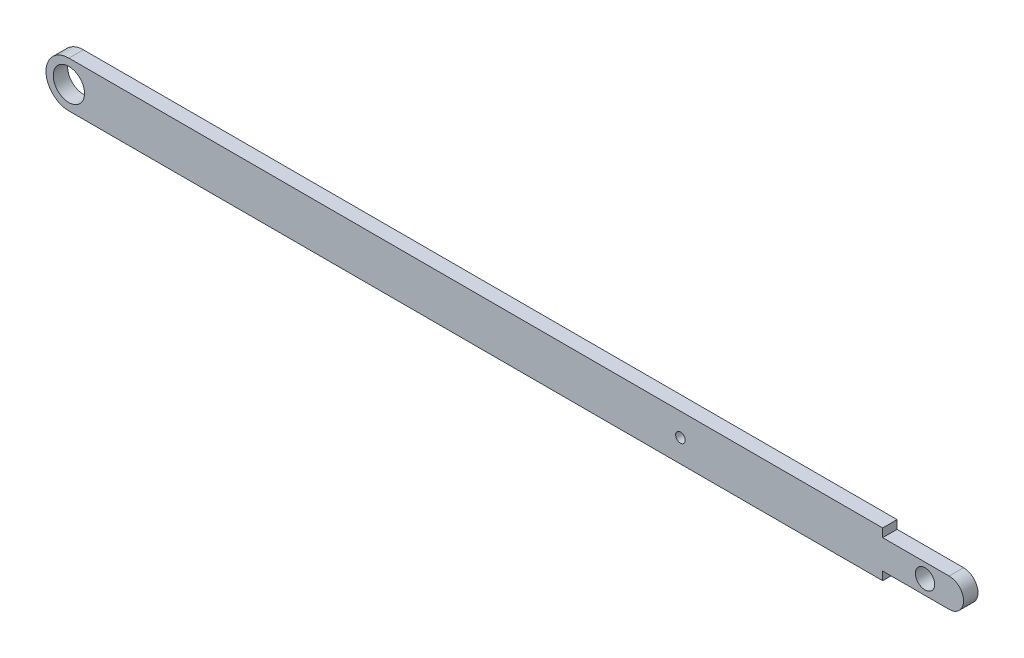
SolidWorks part; units mm, degrees
material "Gray Cast Iron"
ref_plane "Front Plane" through (0, 0, 0) normal (0, 0, 1) x (1, 0, 0)
ref_plane "Top Plane" through (0, 0, 0) normal (0, 1, 0) x (1, 0, 0)
ref_plane "Right Plane" through (0, 0, 0) normal (1, 0, 0) x (0, 0, -1)
sketch "Sketch1" plane through (0, 0, 0) normal (0, 0, 1) x (1, 0, 0)
  line L0 (0, -4.75) -> (169, -4.75)
  line L1 (169, -4.75) -> (169, -3)
  line L2 (169, -3) -> (182.8, -3)
  line L3 (182.8, 3) -> (169, 3)
  line L4 (169, 3) -> (169, 4.75)
  line L5 (169, 4.75) -> (0, 4.75)
  arc A0 (0, 4.75) -> (0, -4.75) centre (0, 0) ccw
  arc A1 (182.8, -3) -> (182.8, 3) centre (182.8, 0) ccw
  dimension "D1" = 4.75
  dimension "D3" = 3
  dimension "D2" = 182.8
  dimension "D4" = 169
extrude "Boss-Extrude1" add sketch "Sketch1" along normal mid plane 3
sketch "Sketch2" plane through (0, 0, 0) normal (0, 0, 1) x (1, 0, 0)
  circle A0 centre (0, 0) radius 3.25
  circle A1 centre (127, 0) radius 1
  circle A2 centre (177.8, 0) radius 2
  dimension "D1" = 6.5
  dimension "D3" = 2
  dimension "D5" = 4
  dimension "D2" = 127
  dimension "D4" = 177.8
extrude "Cut-Extrude1" cut sketch "Sketch2" against normal mid plane 40
ref_axis "Axis1" through (0, 0, 1.65) along (0, 0, -1)
ref_plane "Plane1" through (127, 0, 0) normal (1, 0, 0) x (0, 0, -1)
ref_axis "Axis2" through (127, 0, 1.65) along (0, 0, -1)
